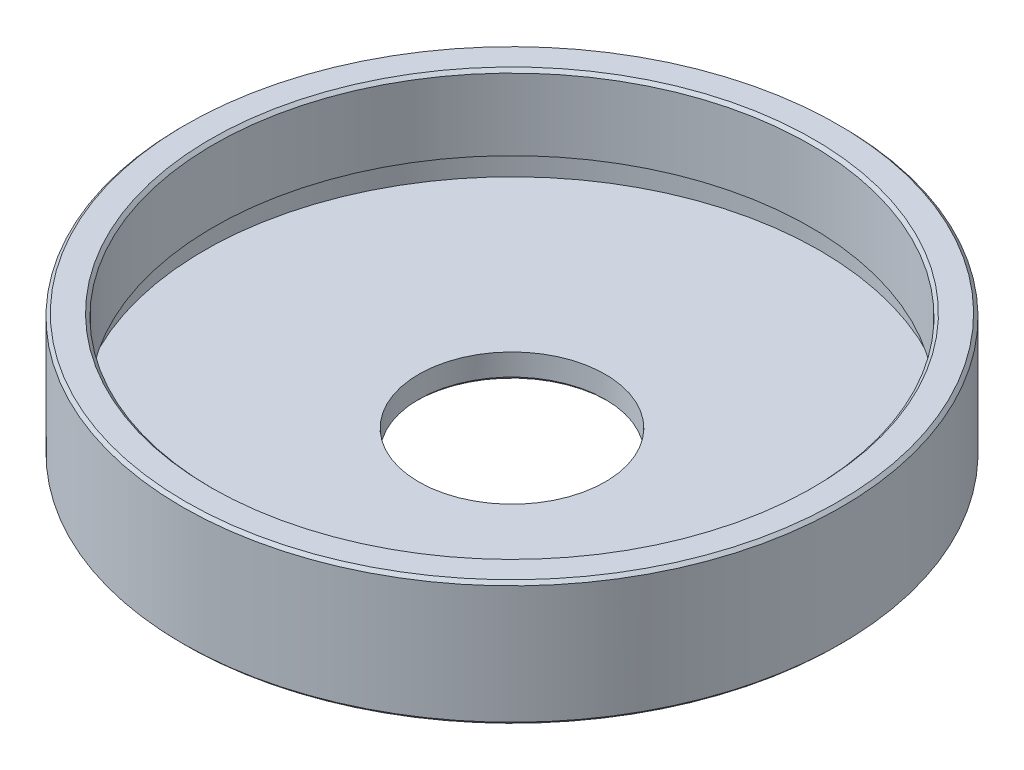
SolidWorks part; units mm, degrees
material "AISI 304"
ref_plane "Спереди" through (0, 0, 0) normal (0, 0, 1) x (1, 0, 0)
ref_plane "Сверху" through (0, 0, 0) normal (0, 1, 0) x (1, 0, 0)
ref_plane "Справа" through (0, 0, 0) normal (1, 0, 0) x (0, 0, -1)
ref_axis "ОсьX" through (-88.99, 0, 0) along (1, 0, 0)
ref_axis "ОсьZ" through (0, 55, 0) along (0, -1, 0)
ref_axis "ОсьY" through (0, 0, -88.99) along (0, 0, 1)
sketch "Эскиз1" plane through (0, 0, 0) normal (0, 0, 1) x (1, 0, 0)
  line L0 (-53, 20) -> (-53, 0)
  line L1 (0, 26.169) -> (0, -22.1581) construction
  line L2 (-53, 0) -> (-15, 0)
  line L3 (-15, 0) -> (-15, 4)
  line L4 (-15, 4) -> (-49.5, 4)
  line L6 (-49.5, 8) -> (-48, 8)
  line L7 (-48, 8) -> (-48, 20)
  line L8 (-48, 20) -> (-53, 20)
  line L11 (-49.5, 8) -> (-49.5, 4)
  dimension "D1" = 106
  dimension "D2" = 20
  dimension "D3" = 96
  dimension "D4" = 30
  dimension "D5" = 4
  dimension "D6" = 1.5
  dimension "D9" = 12
revolve "Повернуть1" add sketch "Эскиз1" angle 360 mid plane about L1
cosmetic thread "Условное изображение резьбы1"
chamfer "Фаска1" distance 0.5 angle 45 4 edges at (0, 0, 15) (0, 0, 53) (0, 20, 53) (0, 20, 48)
